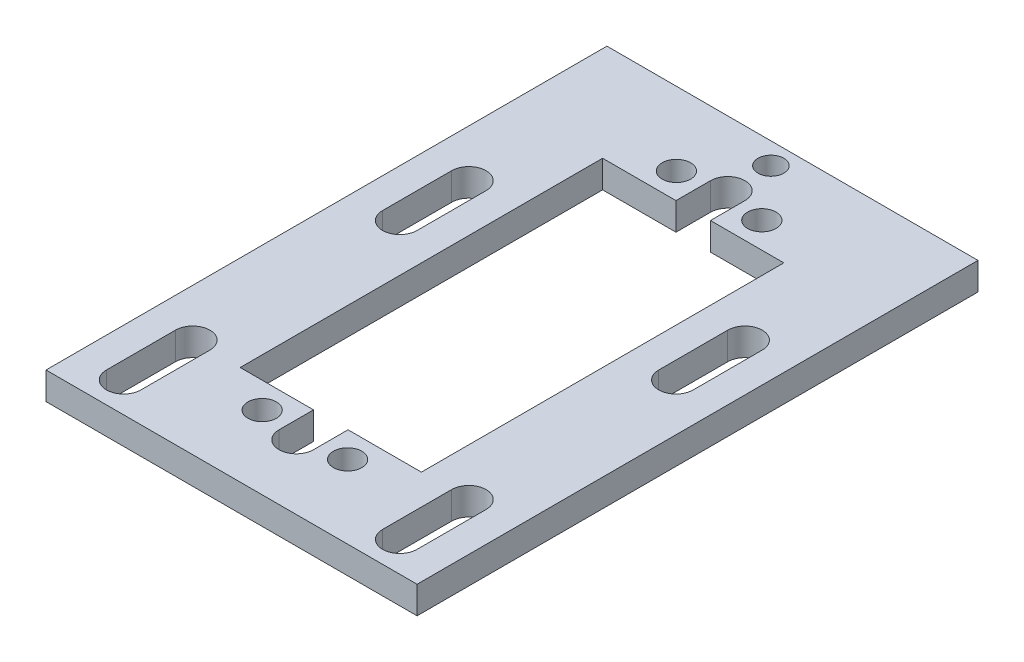
SolidWorks part; units mm, degrees
ref_plane "Front" through (0, 0, 0) normal (0, 0, 1) x (1, 0, 0)
ref_plane "Top" through (0, 0, 0) normal (0, 1, 0) x (1, 0, 0)
ref_plane "Right" through (0, 0, 0) normal (1, 0, 0) x (0, 0, -1)
sketch "Sketch1" plane through (0, 0, 0) normal (0, 1, 0) x (1, 0, 0)
  line L0 (0, 21) -> (0, 25)
  line L1 (-10.5, -21) -> (10.5, -21)
  line L2 (-10.5, -21) -> (-10.5, 21)
  line L3 (-10.5, 21) -> (10.5, 21)
  line L4 (10.5, -21) -> (10.5, 21)
  line L5 (-10.5, -21) -> (10.5, 21) construction
  line L6 (-10.5, 21) -> (10.5, -21) construction
  line L7 (-21.5, 32.5) -> (21.5, 32.5)
  line L8 (-21.5, 32.5) -> (-21.5, -32.5)
  line L9 (-21.5, -32.5) -> (21.5, -32.5)
  line L10 (21.5, 32.5) -> (21.5, -32.5)
  line L11 (-21.5, 32.5) -> (21.5, -32.5) construction
  line L12 (-21.5, -32.5) -> (21.5, 32.5) construction
  line L13 (-2, 25) -> (-2, 21)
  line L14 (2, 25) -> (2, 21)
  line L15 (0, 24) -> (0, -24)
  line L16 (-4.95, -24) -> (4.95, -24)
  line L17 (-4.95, 24) -> (4.95, 24)
  line L18 (-10.5, 0) -> (10.5, 0)
  line L19 (2, -25) -> (2, -21)
  line L20 (-2, -25) -> (-2, -21)
  arc A0 (-2, 25) -> (2, 25) centre (0, 25) cw
  circle A1 centre (4.95, 24) radius 1.65
  circle A2 centre (-4.95, 24) radius 1.65
  circle A3 centre (-4.95, -24) radius 1.65
  circle A4 centre (4.95, -24) radius 1.65
  arc A5 (-2, -25) -> (2, -25) centre (0, -25) ccw
  point P0 (0, 0)
  point P6 (0, 0)
  point P20 (0, 0)
  point P23 (0, -24)
  point P26 (0, 24)
  dimension "D5" = 2
  dimension "D4" = 4
  dimension "D9" = 43
  dimension "D1" = 21
  dimension "D2" = 42
  dimension "D3" = 65
  dimension "D6" = 9.9
  dimension "D7" = 9.9
  dimension "D8" = 48
extrude "Boss-Extrude1" add sketch "Sketch1" along normal blind 3.175 contours L10 L7 L8 L9 A5 L20 A3 L1 L2 L3 L13 A2 A0 L14 A1 L4 L19 A4 region at (0, 0, -31.7206)
sketch "Sketch3" plane through (0, 3.175, 0) normal (0, 1, 0) x (1, 0, 0)
  line L0 (-16, -25) -> (16, -25)
  line L1 (-16, -21) -> (-16, -29) construction
  line L2 (-14, -21) -> (-14, -29)
  line L3 (-18, -21) -> (-18, -29)
  line L4 (0, 0) -> (0, -25)
  line L5 (16, -21) -> (16, -29) construction
  line L6 (14, -21) -> (14, -29)
  line L7 (18, -21) -> (18, -29)
  line L8 (-16, 11) -> (-16, 3) construction
  line L9 (-14, 11) -> (-14, 3)
  line L10 (-18, 11) -> (-18, 3)
  line L11 (16, 11) -> (16, 3) construction
  line L12 (14, 11) -> (14, 3)
  line L13 (18, 11) -> (18, 3)
  arc A0 (-14, -21) -> (-18, -21) centre (-16, -21) ccw
  arc A1 (-18, -29) -> (-14, -29) centre (-16, -29) ccw
  arc A2 (14, -21) -> (18, -21) centre (16, -21) cw
  arc A3 (18, -29) -> (14, -29) centre (16, -29) cw
  arc A4 (-14, 11) -> (-18, 11) centre (-16, 11) ccw
  arc A5 (-18, 3) -> (-14, 3) centre (-16, 3) ccw
  arc A6 (14, 11) -> (18, 11) centre (16, 11) cw
  arc A7 (18, 3) -> (14, 3) centre (16, 3) cw
  point P3 (0, -25)
  point P6 (-16, -25)
  point P15 (16, -25)
  point P24 (-16, 7)
  point P31 (16, 7)
  dimension "D3" = 2
  dimension "D1" = 32
  dimension "D2" = 0
  dimension "D4" = 25
  dimension "D5" = 8
  dimension "D6" = 2
extrude "Cut-Extrude1" cut sketch "Sketch3" against normal blind 3.175 contours L3 A1 L2 A0 | L10 A5 L9 A4 | L13 A7 L12 A6 | L7 A3 L6 A2 region at (-14.1265, 3.175, 27) region at (-16, 3.175, -7)
sketch "Sketch4" plane through (0, 3.175, 0) normal (0, 1, 0) x (1, 0, 0)
  line L0 (-21.5, 32.5) -> (-21.5, -32.5) construction
  line L1 (-21.5, 32.5) -> (21.5, 32.5) construction
  circle A0 centre (0, 30) radius 1.5
  dimension "D1" = 21.5
  dimension "D2" = 2.5
extrude "Cut-Extrude2" cut sketch "Sketch4" against normal blind 10
